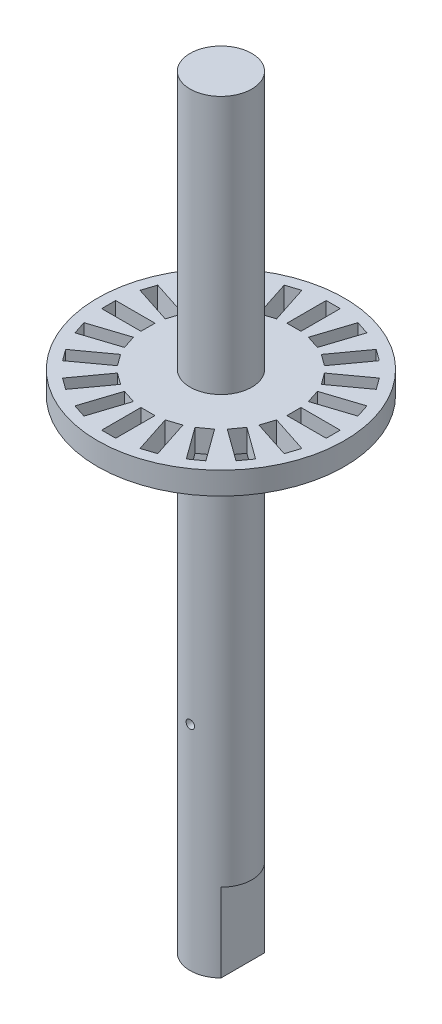
SolidWorks part; units mm, degrees
ref_plane "前视基准面" through (0, 0, 0) normal (0, 0, 1) x (1, 0, 0)
ref_plane "上视基准面" through (0, 0, 0) normal (0, 1, 0) x (1, 0, 0)
ref_plane "右视基准面" through (0, 0, 0) normal (1, 0, 0) x (0, 0, -1)
sketch "草图1" plane through (0, 0, 0) normal (0, 1, 0) x (1, 0, 0)
  circle A0 centre (0, 0) radius 2.75
  dimension "D1" = 5.5
extrude "凸台-拉伸1" add sketch "草图1" along normal blind 61
sketch "草图2" plane through (0, 0, 0) normal (0, -1, 0) x (1, 0, 0)
  line L0 (0, 0) -> (0, -4.8851) construction
  line L2 (-1.95, 1.9391) -> (-1.95, -1.9391)
  line L4 (1.95, 1.9391) -> (1.95, -1.9391)
  arc A0 (-1.95, -1.9391) -> (1.95, -1.9391) centre (0, 0) ccw
  arc A1 (1.95, 1.9391) -> (-1.95, 1.9391) centre (0, 0) ccw
  dimension "D1" = 5.5
  dimension "D2" = 3.9
extrude "凸台-拉伸2" add sketch "草图2" along normal blind 7
sketch "草图4" plane through (0, 0, 0) normal (0, 0, 1) x (1, 0, 0)
  line L0 (1.95, 0) -> (2.75, 0) construction
  circle A0 centre (0, 12) radius 0.375
  dimension "D1" = 0.75
  dimension "D2" = 12
extrude "切除-拉伸1" cut sketch "草图4" against normal mid plane 10
sketch "草图6" plane through (0, 61, 0) normal (0, 1, 0) x (1, 0, 0)
  line L2 (0, 11) -> (0, 0) construction
  line L3 (2.4958, 9.7037) -> (3.6846, 9.3174)
  line L42 (-0.625, 10) -> (0.625, 10)
  line L43 (-0.625, 10) -> (-0.625, 6.5)
  line L44 (-0.625, 6.5) -> (0.625, 6.5)
  line L45 (0.625, 10) -> (0.625, 6.5)
  line L46 (2.4958, 9.7037) -> (1.4142, 6.375)
  line L47 (1.4142, 6.375) -> (2.603, 5.9887)
  line L48 (3.6846, 9.3174) -> (2.603, 5.9887)
  line L49 (5.3722, 8.4575) -> (6.3835, 7.7228)
  line L50 (5.3722, 8.4575) -> (3.315, 5.626)
  line L51 (3.315, 5.626) -> (4.3262, 4.8912)
  line L52 (6.3835, 7.7228) -> (4.3262, 4.8912)
  line L53 (7.7228, 6.3835) -> (8.4575, 5.3722)
  line L54 (7.7228, 6.3835) -> (4.8912, 4.3262)
  line L55 (4.8912, 4.3262) -> (5.626, 3.315)
  line L56 (8.4575, 5.3722) -> (5.626, 3.315)
  line L57 (9.3174, 3.6846) -> (9.7037, 2.4958)
  line L58 (9.3174, 3.6846) -> (5.9887, 2.603)
  line L59 (5.9887, 2.603) -> (6.375, 1.4142)
  line L60 (9.7037, 2.4958) -> (6.375, 1.4142)
  line L61 (10, 0.625) -> (10, -0.625)
  line L62 (10, 0.625) -> (6.5, 0.625)
  line L63 (6.5, 0.625) -> (6.5, -0.625)
  line L64 (10, -0.625) -> (6.5, -0.625)
  line L65 (9.7037, -2.4958) -> (9.3174, -3.6846)
  line L66 (9.7037, -2.4958) -> (6.375, -1.4142)
  line L67 (6.375, -1.4142) -> (5.9887, -2.603)
  line L68 (9.3174, -3.6846) -> (5.9887, -2.603)
  line L69 (8.4575, -5.3722) -> (7.7228, -6.3835)
  line L70 (8.4575, -5.3722) -> (5.626, -3.315)
  line L71 (5.626, -3.315) -> (4.8912, -4.3262)
  line L72 (7.7228, -6.3835) -> (4.8912, -4.3262)
  line L73 (6.3835, -7.7228) -> (5.3722, -8.4575)
  line L74 (6.3835, -7.7228) -> (4.3262, -4.8912)
  line L75 (4.3262, -4.8912) -> (3.315, -5.626)
  line L76 (5.3722, -8.4575) -> (3.315, -5.626)
  line L77 (3.6846, -9.3174) -> (2.4958, -9.7037)
  line L78 (3.6846, -9.3174) -> (2.603, -5.9887)
  line L79 (2.603, -5.9887) -> (1.4142, -6.375)
  line L80 (2.4958, -9.7037) -> (1.4142, -6.375)
  line L81 (0.625, -10) -> (-0.625, -10)
  line L82 (0.625, -10) -> (0.625, -6.5)
  line L83 (0.625, -6.5) -> (-0.625, -6.5)
  line L84 (-0.625, -10) -> (-0.625, -6.5)
  line L85 (-2.4958, -9.7037) -> (-3.6846, -9.3174)
  line L86 (-2.4958, -9.7037) -> (-1.4142, -6.375)
  line L87 (-1.4142, -6.375) -> (-2.603, -5.9887)
  line L88 (-3.6846, -9.3174) -> (-2.603, -5.9887)
  line L89 (-5.3722, -8.4575) -> (-6.3835, -7.7228)
  line L90 (-5.3722, -8.4575) -> (-3.315, -5.626)
  line L91 (-3.315, -5.626) -> (-4.3262, -4.8912)
  line L92 (-6.3835, -7.7228) -> (-4.3262, -4.8912)
  line L93 (-7.7228, -6.3835) -> (-8.4575, -5.3722)
  line L94 (-7.7228, -6.3835) -> (-4.8912, -4.3262)
  line L95 (-4.8912, -4.3262) -> (-5.626, -3.315)
  line L96 (-8.4575, -5.3722) -> (-5.626, -3.315)
  line L97 (-9.3174, -3.6846) -> (-9.7037, -2.4958)
  line L98 (-9.3174, -3.6846) -> (-5.9887, -2.603)
  line L99 (-5.9887, -2.603) -> (-6.375, -1.4142)
  line L100 (-9.7037, -2.4958) -> (-6.375, -1.4142)
  line L101 (-10, -0.625) -> (-10, 0.625)
  line L102 (-10, -0.625) -> (-6.5, -0.625)
  line L103 (-6.5, -0.625) -> (-6.5, 0.625)
  line L104 (-10, 0.625) -> (-6.5, 0.625)
  line L105 (-9.7037, 2.4958) -> (-9.3174, 3.6846)
  line L106 (-9.7037, 2.4958) -> (-6.375, 1.4142)
  line L107 (-6.375, 1.4142) -> (-5.9887, 2.603)
  line L108 (-9.3174, 3.6846) -> (-5.9887, 2.603)
  line L109 (-8.4575, 5.3722) -> (-7.7228, 6.3835)
  line L110 (-8.4575, 5.3722) -> (-5.626, 3.315)
  line L111 (-5.626, 3.315) -> (-4.8912, 4.3262)
  line L112 (-7.7228, 6.3835) -> (-4.8912, 4.3262)
  line L113 (-6.3835, 7.7228) -> (-5.3722, 8.4575)
  line L114 (-6.3835, 7.7228) -> (-4.3262, 4.8912)
  line L115 (-4.3262, 4.8912) -> (-3.315, 5.626)
  line L116 (-5.3722, 8.4575) -> (-3.315, 5.626)
  line L117 (-3.6846, 9.3174) -> (-2.4958, 9.7037)
  line L118 (-3.6846, 9.3174) -> (-2.603, 5.9887)
  line L119 (-2.603, 5.9887) -> (-1.4142, 6.375)
  line L120 (-2.4958, 9.7037) -> (-1.4142, 6.375)
  circle A0 centre (0, 0) radius 11
  point P88 (0, 0)
  dimension "D1" = 22
  dimension "D3" = 10
  dimension "D4" = 6.5
  dimension "D2" = 1.25
extrude "凸台-拉伸4" add sketch "草图6" along normal blind 2 from offset 25 offset against normal yes
